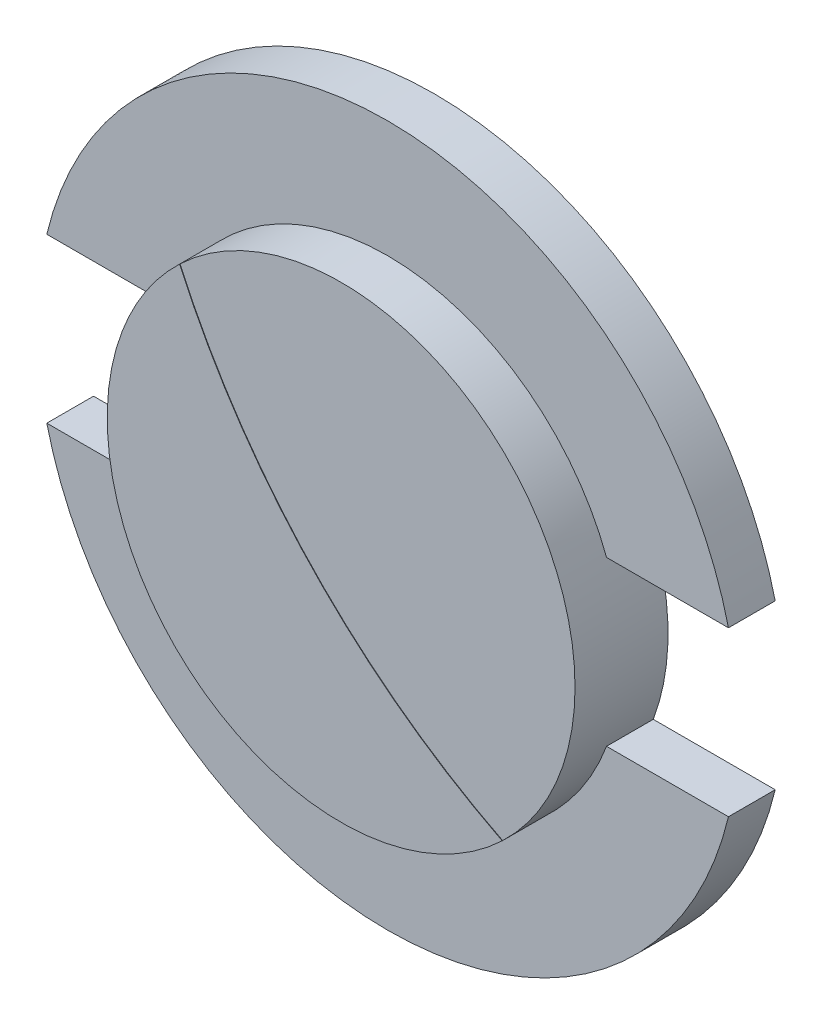
SolidWorks part; units mm, degrees
ref_plane "Front Plane" through (0, 0, 0) normal (1, 0, 0) x (0, 1, 0)
ref_plane "Top Plane" through (0, 0, 0) normal (0, 0, 1) x (0, 1, 0)
ref_plane "Right Plane" through (0, 0, 0) normal (0, 1, 0) x (-1, 0, 0)
sketch "Sketch1" plane through (0, 0, 0) normal (0, 0, 1) x (0, 1, 0)
  circle A0 centre (0, 0) radius 7.5
  dimension "D1" = 15
extrude "Boss-Extrude1" add sketch "Sketch1" along normal blind 1
sketch "Sketch2" plane through (0, 0, 1) normal (0, 0, 1) x (1, 0, 0)
  circle A0 centre (0, 0) radius 5
  dimension "D1" = 10
extrude "Boss-Extrude2" add sketch "Sketch2" along normal blind 1
sketch "Sketch3" plane through (0, 0, 1) normal (0, 0, 1) x (1, 0, 0)
  line L1 (-7.5, 1.75) -> (7.5, 1.75)
  line L2 (-7.5, 1.75) -> (-7.5, -1.75)
  line L3 (-7.5, -1.75) -> (7.5, -1.75)
  line L4 (7.5, 1.75) -> (7.5, -1.75)
  line L5 (-7.5, 1.75) -> (7.5, -1.75) construction
  line L6 (-7.5, -1.75) -> (7.5, 1.75) construction
  circle A0 centre (0, 0) radius 7.5 construction
  point P0 (0, 0)
  circle M5 centre (0, 0) radius 5
  circle M6 centre (0, 0) radius 7.5
  dimension "D1" = 3.5
extrude "Cut-Extrude2" cut sketch "Sketch3" against normal up to next contours L3 L1 M6 M5 | L3 L1 M5 M6 region at (-6.1627, 0, 1) region at (6.1627, 0, 1)
sketch "Sketch4" plane through (0, 0, 2) normal (0, 0, 1) x (0, -1, 0)
  line L0 (-3.6182, -3.4509) -> (3.6182, 3.4509) construction
  circle A0 centre (-9.7607, 10.2337) radius 15
  circle A1 centre (0, 0) radius 5 construction
  point P7 (0, 0)
  point P8 (0, 0)
  point P9 (3.8802, 3.1534)
  point P10 (3.6182, 3.4509)
  dimension "D1" = 30
extrude "Cut-Extrude3" cut sketch "Sketch4" against normal blind 0.01
